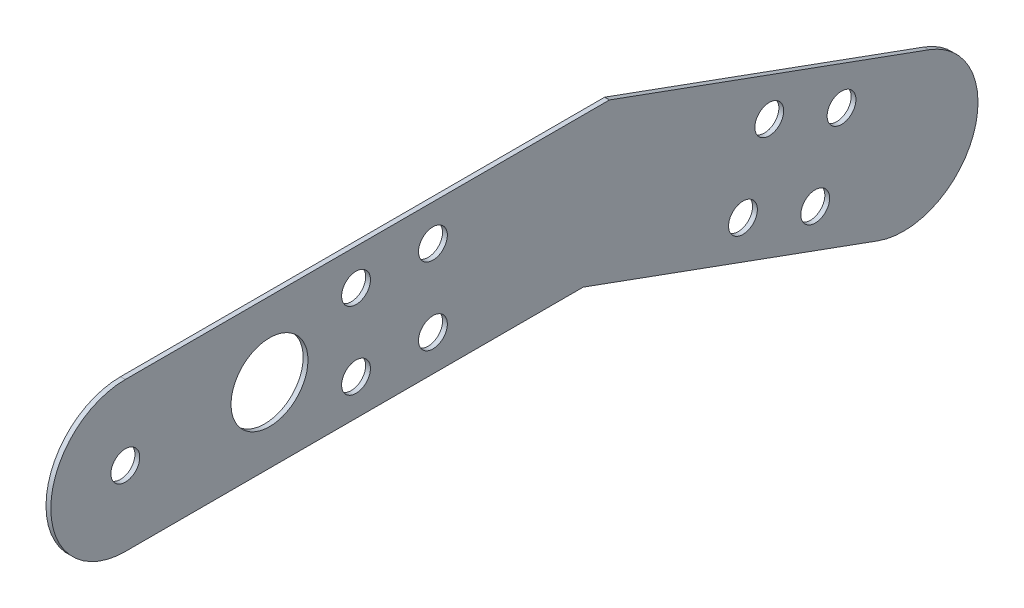
SolidWorks part; units mm, degrees
ref_plane "Front Plane" through (0, 0, 0) normal (0, 0, 1) x (1, 0, 0)
ref_plane "Top Plane" through (0, 0, 0) normal (0, 1, 0) x (1, 0, 0)
ref_plane "Right Plane" through (0, 0, 0) normal (1, 0, 0) x (0, 0, -1)
sketch "Croquis1" plane through (0, 0, 0) normal (1, 0, 0) x (0, 0, -1)
  line L0 (-43.6048, 13.556) -> (5.3952, 13.556) construction
  line L1 (5.3952, 13.556) -> (37.3448, 1.9273) construction
  line L2 (-19.6048, 1.0218) -> (-19.6048, 27.4624) construction
  line L3 (19.3614, 0.2253) -> (30.0972, 29.7217) construction
  line L6 (-43.6048, 5.806) -> (4.0287, 5.806)
  line L7 (4.0287, 5.806) -> (34.6941, -5.3553)
  line L8 (-43.6048, 21.306) -> (6.7618, 21.306)
  line L9 (6.7618, 21.306) -> (39.9954, 9.2099)
  circle A0 centre (-19.6048, 17.556) radius 1.5
  circle A1 centre (-19.6048, 9.556) radius 1.5
  circle A2 centre (-43.6048, 13.556) radius 1.5
  arc A3 (-43.6048, 5.806) -> (-43.6048, 21.306) centre (-43.6048, 13.556) cw
  arc A4 (34.6941, -5.3553) -> (39.9954, 9.2099) centre (37.3448, 1.9273) ccw
  circle A5 centre (23.3801, 11.2667) radius 1.5
  circle A6 centre (20.644, 3.7492) radius 1.5
  circle A7 centre (-28.6048, 13.556) radius 4
  circle A10 centre (30.8977, 8.5306) radius 1.5
  circle A11 centre (28.1615, 1.013) radius 1.5
  circle A12 centre (-11.6048, 17.556) radius 1.5
  circle A13 centre (-11.6048, 9.556) radius 1.5
  point P24 (-40.8546, 9.556)
  point P25 (6.6188, 9.556)
  point P26 (34.122, 2.1865)
  point P27 (-40.8546, 17.556)
  point P28 (7.672, 17.556)
  point P29 (36.1925, 9.9139)
  dimension "D6" = 3
  dimension "D4" = 3
  dimension "D9" = 3
  dimension "D11" = 8
  dimension "D15" = 3
  dimension "D17" = 3
  dimension "D16" = 24
  dimension "D1" = 49
  dimension "D2" = 34
  dimension "D3" = 200
  dimension "D5" = 8
  dimension "D10" = 8
  dimension "D12" = 15
  dimension "D18" = 8
  dimension "D13" = 8
  dimension "D14" = 8
  dimension "D7" = 7.75
  dimension "D8" = 7.75
sheet metal parameters "Chapa metálica1" thickness 0.5 parameters "D1"=0.5, "Espesor"=0.5
base flange "Brida base1" sketch "Croquis1" thickness 0.5 reverse thickness direction no parameters "D1"=0.5
flat pattern "Chapa desplegada1" [suppressed]
sketch "Líneas de pliegue1" plane through (0, 0, 0) normal (0, 1, 0) x (-1, 0, 0)
sketch3d "Cuadro delimitador1" [suppressed]
  line L0 (-87.5186, -20.398, 0) -> (8.7714, -6.5697, 0) construction
  line L1 (-90.7285, 1.9536, 0) -> (5.5615, 15.7819, 0) construction
  line L2 (-87.5186, -20.398, 0) -> (-90.7285, 1.9536, 0) construction
  line L3 (8.7714, -6.5697, 0) -> (5.5615, 15.7819, 0) construction
